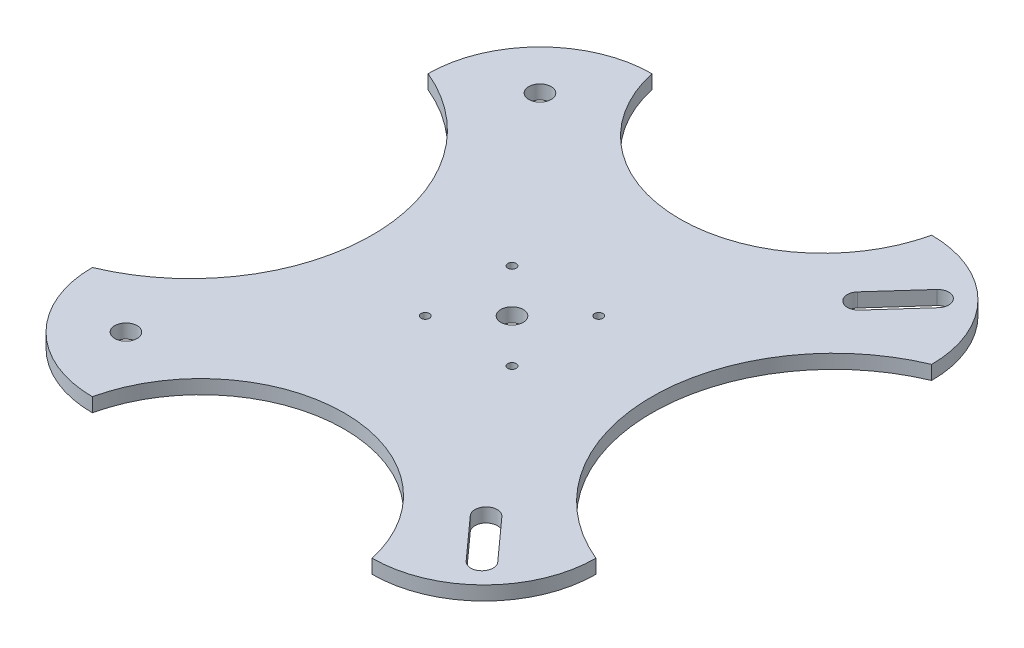
SolidWorks part; units mm, degrees
ref_plane "Piano frontale" through (0, 0, 0) normal (0, 0, 1) x (1, 0, 0)
ref_plane "Piano superiore" through (0, 0, 0) normal (0, 1, 0) x (1, 0, 0)
ref_plane "Piano destro" through (0, 0, 0) normal (1, 0, 0) x (0, 0, -1)
sketch "Schizzo1" plane through (0, 0, 0) normal (0, 1, 0) x (1, 0, 0)
  line L0 (-90, 100) -> (-50, 100) construction
  line L1 (-90, 100) -> (90, 100) construction
  line L2 (-90, 100) -> (-90, -100) construction
  line L3 (-90, -100) -> (90, -100) construction
  line L4 (90, 100) -> (90, -100) construction
  line L5 (90, 100) -> (50, 100) construction
  line L6 (-90, 100) -> (-90, 60) construction
  line L7 (90, 100) -> (90, 60) construction
  line L8 (-90, -100) -> (-90, -60) construction
  line L9 (-90, -100) -> (-50, -100) construction
  line L10 (90, -100) -> (50, -100) construction
  line L11 (90, -100) -> (90, -60) construction
  line L12 (-50, 100) -> (-50, -100) construction
  line L13 (-90, -60) -> (90, -60) construction
  line L14 (-90, 60) -> (90, 60) construction
  line L15 (50, 100) -> (50, -100) construction
  line L16 (-90, 100) -> (90, -100) construction
  line L17 (-90, -100) -> (90, 100) construction
  line L18 (-64, 74) -> (64, -74) construction
  line L19 (-64, -74) -> (64, 74) construction
  line L20 (73.6628, -78.7571) -> (60.2835, -63.8912)
  line L21 (67.7165, -84.1088) -> (54.3372, -69.2429)
  line L22 (61.0268, -76.6759) -> (66.9732, -71.3241) construction
  line L23 (60.2835, 63.8912) -> (73.6628, 78.7571)
  line L24 (54.3372, 69.2429) -> (67.7165, 84.1088)
  line L25 (61.0268, 76.6759) -> (66.9732, 71.3241) construction
  arc A0 (-50, 100) -> (-90, 60) centre (-50, 60) ccw
  arc A1 (50, 100) -> (90, 60) centre (50, 60) cw
  arc A2 (90, -60) -> (50, -100) centre (50, -60) cw
  arc A3 (-50, -100) -> (-90, -60) centre (-50, -60) cw
  arc A4 (-90, 60) -> (-90, -60) centre (-115, 0) cw
  arc A5 (90, 60) -> (90, -60) centre (115, 0) ccw
  arc A6 (50, -100) -> (-50, -100) centre (0, -111.25) ccw
  arc A7 (50, 100) -> (-50, 100) centre (0, 111.25) cw
  circle A8 centre (-64, 74) radius 4
  circle A9 centre (64, 74) radius 4 construction
  circle A10 centre (64, -74) radius 4 construction
  circle A11 centre (-64, -74) radius 4
  circle A12 centre (0, 0) radius 4
  arc A13 (60.2835, -63.8912) -> (54.3372, -69.2429) centre (57.3104, -66.5671) ccw
  arc A14 (73.6628, -78.7571) -> (67.7165, -84.1088) centre (70.6896, -81.4329) cw
  arc A15 (73.6628, 78.7571) -> (67.7165, 84.1088) centre (70.6896, 81.4329) ccw
  arc A16 (60.2835, 63.8912) -> (54.3372, 69.2429) centre (57.3104, 66.5671) cw
  dimension "D4" = 8
  dimension "D5" = 14
  dimension "D6" = 14
  dimension "D7" = 14
  dimension "D8" = 14
  dimension "D9" = 14
  dimension "D10" = 14
  dimension "D11" = 14
  dimension "D12" = 14
  dimension "D13" = 8
  dimension "D1" = 180
  dimension "D2" = 200
  dimension "D3" = 40
  dimension "D14" = 8
  dimension "D15" = 20
  dimension "D16" = 20
extrude "Estrusione-Estrusione1" add sketch "Schizzo1" along normal blind 5
sketch "Schizzo2" plane through (0, 5, 0) normal (0, 1, 0) x (1, 0, 0)
  line L0 (-15.5, 15.5) -> (-15.5, -15.5) construction
  line L1 (-15.5, -15.5) -> (15.5, -15.5) construction
  line L2 (15.5, -15.5) -> (15.5, 15.5) construction
  line L3 (15.5, 15.5) -> (-15.5, 15.5) construction
  circle A0 centre (-15.5, 15.5) radius 1.5
  circle A1 centre (15.5, 15.5) radius 1.5
  circle A2 centre (15.5, -15.5) radius 1.5
  circle A3 centre (-15.5, -15.5) radius 1.5
  circle A4 centre (0, 0) radius 4 construction
  dimension "D2" = 3
  dimension "D1" = 31
  dimension "D3" = 15.5
  dimension "D4" = 15.5
extrude "Taglio-Estrusione1" cut sketch "Schizzo2" against normal through all
